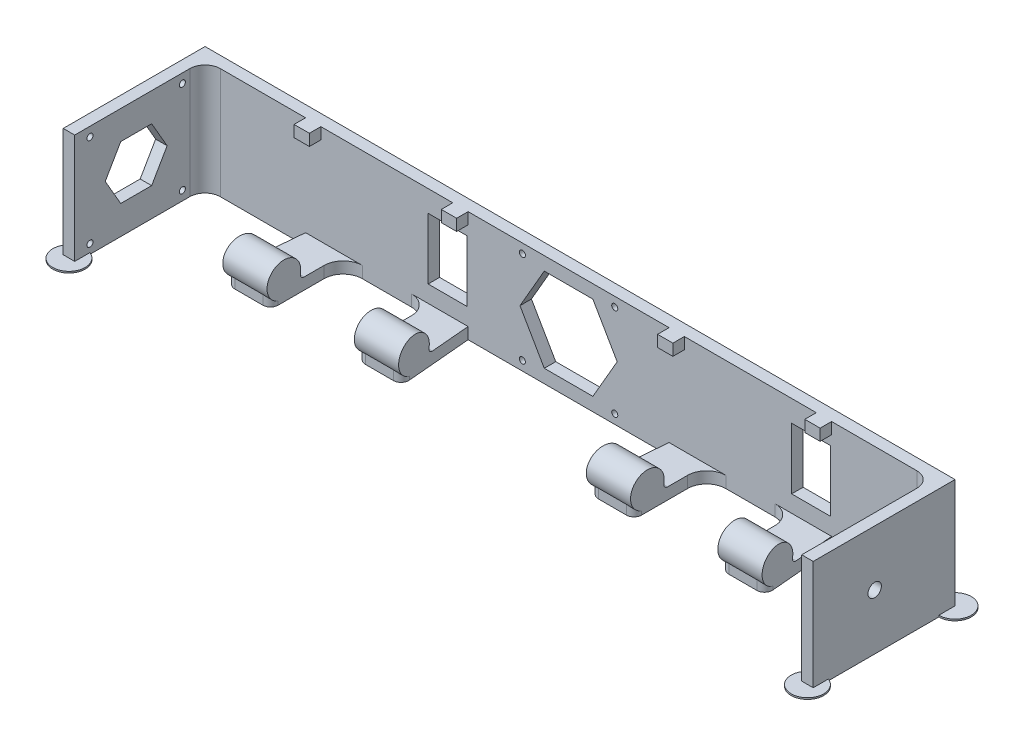
SolidWorks part; units mm, degrees
note: The reader was unsure of these and kept them because the rebuilt part matched: shared geometry of "Sketch10<3>".
ref_plane "Front Plane" through (0, 0, 0) normal (0, 0, 1) x (1, 0, 0)
ref_plane "Top Plane" through (0, 0, 0) normal (0, 1, 0) x (1, 0, 0)
ref_plane "Right Plane" through (0, 0, 0) normal (1, 0, 0) x (0, 0, -1)
sketch "Sketch1" plane through (0, 0, 0) normal (0, 0, 1) x (1, 0, 0)
  line L1 (-95, 14.5) -> (95, 14.5)
  line L2 (-95, 14.5) -> (-95, -14.5)
  line L3 (-95, -14.5) -> (95, -14.5)
  line L4 (95, 14.5) -> (95, -14.5)
  line L5 (-95, 14.5) -> (95, -14.5) construction
  line L6 (-95, -14.5) -> (95, 14.5) construction
  point P0 (0, 0)
  dimension "D1" = 190
  dimension "D2" = 29
extrude "Boss-Extrude1" add sketch "Sketch1" along normal blind 3
sketch "Sketch2" plane through (0, 0, 3) normal (0, 0, 1) x (1, 0, 0)
  line L0 (95, -14.5) -> (95, 14.5) construction
  line L1 (-95, 14.5) -> (95, 14.5)
  line L2 (-95, 14.5) -> (-95, 11.5)
  line L3 (-95, 11.5) -> (95, 11.5)
  line L4 (95, 14.5) -> (95, 11.5)
  dimension "D1" = 3
extrude "Boss-Extrude2" add sketch "Sketch2" along normal blind 3
sketch "Sketch3" plane through (0, 0, 3) normal (0, 0, 1) x (1, 0, 0)
  line L0 (95, -14.5) -> (95, 11.5) construction
  line L1 (-95, -14.5) -> (95, -14.5)
  line L2 (-95, -14.5) -> (-95, -11.5)
  line L3 (-95, -11.5) -> (95, -11.5)
  line L4 (95, -14.5) -> (95, -11.5)
  dimension "D1" = 3
extrude "Boss-Extrude3" add sketch "Sketch3" along normal blind 19
sketch "Sketch4" plane through (-95, 0, 0) normal (-1, 0, 0) x (0, 0, 1)
  line L0 (3, 11.5) -> (3, -11.5) construction
  line L2 (22, -11.5) -> (3, -11.5) construction
  line L3 (6, 14.5) -> (0, 14.5) construction
  circle A0 centre (18.5, -9.4) radius 4.4
  arc A1 (3, 11.5) -> (8.2117, 14.5) centre (18.5, -9.4) cw construction
  point P4 (18.5, -5)
  dimension "D1" = 8.8
  dimension "D3" = 6.5
  dimension "D2" = 15.5
extrude "Boss-Extrude4" add sketch "Sketch4" against normal up to vertex (190 mm away) up to point (95, -11.5, 22)
fillet "Fillet1" radius 1 1 edges at (0, -11.5, 14.6335)
sketch "Sketch5" plane through (0, 0, 3) normal (0, 0, 1) x (1, 0, 0)
  line L1 (-95, -14.5) -> (-70.4, -14.5)
  line L2 (-95, -14.5) -> (-95, -5)
  line L3 (-95, -5) -> (-70.4, -5)
  line L4 (-70.4, -14.5) -> (-70.4, -5)
  line L5 (-58.9, -14.5) -> (-36.1, -14.5)
  line L6 (-58.9, -14.5) -> (-58.9, -5)
  line L7 (-58.9, -5) -> (-36.1, -5)
  line L8 (-36.1, -14.5) -> (-36.1, -5)
  line L9 (0, -5) -> (0, 0) construction
  line L10 (-24.6, -14.5) -> (24.6, -14.5)
  line L11 (-24.6, -14.5) -> (-24.6, -5)
  line L12 (-24.6, -5) -> (24.6, -5)
  line L13 (24.6, -14.5) -> (24.6, -5)
  line L14 (36.1, -14.5) -> (36.1, -5)
  line L15 (58.9, -5) -> (36.1, -5)
  line L16 (58.9, -14.5) -> (58.9, -5)
  line L17 (58.9, -14.5) -> (36.1, -14.5)
  line L18 (70.4, -14.5) -> (70.4, -5)
  line L19 (95, -5) -> (70.4, -5)
  line L20 (95, -14.5) -> (95, -5)
  line L21 (95, -14.5) -> (70.4, -14.5)
  line L22 (95, -5) -> (-95, -5) construction
  line L23 (-95, -14.5) -> (95, -14.5) construction
  dimension "D1" = 11.5
  dimension "D2" = 11.5
  dimension "D3" = 95
  dimension "D4" = 22.8
  dimension "D5" = 45.8
extrude "Cut-Extrude1" cut sketch "Sketch5" along normal through all
sketch "Sketch8" plane through (0, 0, 3) normal (0, 0, 1) x (1, 0, 0)
  line L1 (6.3509, -11) -> (12.7017, 0)
  line L2 (12.7017, 0) -> (6.3509, 11)
  line L3 (6.3509, 11) -> (-6.3509, 11)
  line L4 (-6.3509, 11) -> (-12.7017, 0)
  line L5 (-12.7017, 0) -> (-6.3509, -11)
  line L6 (-6.3509, -11) -> (6.3509, -11)
  circle A0 centre (-12.0668, -12.0668) radius 0.7937
  circle A1 centre (-12.0668, 12.0668) radius 0.7937
  circle A2 centre (12.0668, 12.0668) radius 0.7937
  circle A3 centre (12.0668, -12.0668) radius 0.7937
  circle A4 centre (0, 0) radius 11 construction
  point P10 (0, 0)
  dimension "D2" = 34.13
  dimension "D3" = 1.5875
  dimension "D4" = 22
  dimension "D1" = 4
extrude "Cut-Extrude3" cut sketch "Sketch8" against normal up to next
sketch "Sketch9" plane through (0, 0, 3) normal (0, 0, 1) x (1, 0, 0)
  line L0 (-58.9, -14.5) -> (-36.1, -14.5) construction
  line L1 (-36.7, 8.9) -> (-26.5, 8.9)
  line L2 (-36.7, 8.9) -> (-36.7, -7.1)
  line L3 (-36.7, -7.1) -> (-26.5, -7.1)
  line L4 (-26.5, 8.9) -> (-26.5, -7.1)
  line L5 (-36.1, -14.5) -> (-36.1, -11.5) construction
  line L6 (-31.6, -5.1) -> (-31.6, -7.1) construction
  line L7 (-24.6, -11.5) -> (70.4, -11.5) construction
  line L8 (15.9, -11.5) -> (15.9, -1.9782) construction
  line L9 (68.5, 8.9) -> (68.5, -7.1)
  line L10 (68.5, -7.1) -> (58.3, -7.1)
  line L11 (58.3, 8.9) -> (58.3, -7.1)
  line L12 (68.5, 8.9) -> (58.3, 8.9)
  line L13 (-26.5, 8.9) -> (68.5, 8.9) construction
  point P4 (-31.6, -5.1)
  dimension "D1" = 10.2
  dimension "D2" = 16
  dimension "D3" = 9.4
  dimension "D4" = 4.5
  dimension "D5" = 2
extrude "Cut-Extrude4" cut sketch "Sketch9" against normal up to next
draft "Draft1" type of draft neutral plane draft angle 5 faces to draft 4 face at (70.4, -11.4205, 13.1781) face at (24.6, -11.4205, 13.1781) face at (-24.6, -11.4205, 13.1781) face at (-70.4, -11.4205, 13.1781) neutral plane through (0, 0, 22) neutral plane normal (0, 0, 1) reverse direction yes parameters "D1"=5
fillet "Fillet2" radius 5 4 edges at (36.1, -13, 3) (58.9, -13, 3) (-36.1, -13, 3) (-58.9, -13, 3)
fillet "Fillet3" radius 2 8 edges at (70.4, -13.2832, 22) (58.9, -13.2832, 22) (36.1, -13.2832, 22) (24.6, -13.2832, 22) (-24.6, -13.2832, 22) (-36.1, -13.2832, 22) (-58.9, -13.2832, 22) (-70.4, -13.2832, 22)
sketch "Sketch10" plane through (-95, 0, 0) normal (-1, 0, 0) x (0, 0, 1)
  line L0 (3, -14.5) -> (0, -14.5) construction
  line L1 (0, 14.5) -> (8.9297, 14.5)
  line L2 (0, 14.5) -> (0, -14.5)
  line L3 (0, -14.5) -> (37.0703, -14.5)
  line L5 (3, 11.5) -> (3, -14.5) construction
  line L6 (6, 11.5) -> (3, 11.5) construction
  line L7 (8.9297, 14.5) -> (37.0703, 14.5)
  line L8 (37.0703, 14.5) -> (37.0703, -14.5)
  line L9 (29.0829, 0) -> (25.0415, 7)
  line L10 (25.0415, 7) -> (16.9585, 7)
  line L11 (16.9585, 7) -> (12.9171, 0)
  line L12 (12.9171, 0) -> (16.9585, -7)
  line L13 (16.9585, -7) -> (25.0415, -7)
  line L14 (25.0415, -7) -> (29.0829, 0)
  circle A1 centre (8.9297, 12.0703) radius 0.7938
  circle A2 centre (33.0703, 12.0703) radius 0.7937
  circle A3 centre (33.0703, -12.0703) radius 0.7937
  circle A4 centre (8.9297, -12.0703) radius 0.7937
  circle A5 centre (21, 0) radius 1.75
  circle A6 centre (21, 0) radius 7 construction
  point P30 (21, 0)
  dimension "D4" = 4
  dimension "D6" = 34.14
  dimension "D7" = 1.5875
  dimension "D8" = 3.5
  dimension "D1" = 14
  dimension "D2" = 11.5
  dimension "D3" = 18
  dimension "D5" = 4
extrude "Boss-Extrude5" add sketch "Sketch10" along normal blind 3
extrude "Boss-Extrude8" add sketch "Sketch10<3>" against normal blind 3 from vertex at -190 contours L7 L8 L3 L2 L1 | A5
sketch "Sketch10<3>" plane through (-95, 0, 0) normal (-1, 0, 0) x (0, 0, 1) same geometry as "Sketch10"
sketch "Sketch12" plane through (0, 0, 3) normal (0, 0, 1) x (1, 0, 0)
  line L0 (95, 14.5) -> (-95, 14.5) construction
  line L1 (-95, 11.5) -> (-68.7377, 11.5)
  line L2 (-95, 11.5) -> (-95, 14.5)
  line L3 (-95, 14.5) -> (-68.7377, 14.5)
  line L4 (-68.7377, 11.5) -> (-68.7377, 14.5)
  line L5 (-95, 11.5) -> (-12.6225, 11.5) construction
  line L7 (-95, 11.5) -> (-12.6225, 11.5) construction
  line L8 (-64.7377, 14.5) -> (-30.2623, 14.5)
  line L9 (-64.7377, 14.5) -> (-64.7377, 11.5)
  line L10 (-64.7377, 11.5) -> (-30.2623, 11.5)
  line L11 (-30.2623, 14.5) -> (-30.2623, 11.5)
  line L12 (12.6225, 11.5) -> (95, 11.5) construction
  line L13 (-26.2623, 14.5) -> (26.2623, 14.5)
  line L14 (-26.2623, 14.5) -> (-26.2623, 11.5)
  line L15 (-26.2623, 11.5) -> (26.2623, 11.5)
  line L16 (26.2623, 14.5) -> (26.2623, 11.5)
  line L17 (30.2623, 14.5) -> (64.7377, 14.5)
  line L18 (30.2623, 14.5) -> (30.2623, 11.5)
  line L19 (30.2623, 11.5) -> (64.7377, 11.5)
  line L20 (64.7377, 14.5) -> (64.7377, 11.5)
  line L21 (68.7377, 14.5) -> (95, 14.5)
  line L22 (68.7377, 14.5) -> (68.7377, 11.5)
  line L23 (68.7377, 11.5) -> (95, 11.5)
  line L24 (95, 14.5) -> (95, 11.5)
  line L26 (68.7377, -11.5) -> (68.7377, -14.5) construction
  line L27 (-68.7377, -14.5) -> (-68.7377, -11.5) construction
  line L28 (-26.2623, -11.5) -> (-26.2623, -14.5) construction
  line L29 (26.2623, -14.5) -> (26.2623, -11.5) construction
  line L30 (95, 11.5) -> (95, 14.5) construction
  line L31 (-95, 14.5) -> (-95, 11.5) construction
  dimension "D4" = 4
  dimension "D5" = 4
  dimension "D6" = 4
  dimension "D7" = 4
extrude "Cut-Extrude5" cut sketch "Sketch12" along normal through all
sketch "Sketch13" plane through (0, -14.5, 0) normal (0, -1, 0) x (1, 0, 0)
  line L0 (-98, 37.0703) -> (-95, 37.0703) construction
  line L1 (98, 37.0703) -> (95, 37.0703) construction
  circle A0 centre (-96.5, 37.0703) radius 4.2426
  circle A1 centre (96.5, 37.0703) radius 4.2426
  circle A2 centre (98, 0) radius 4.2426
  circle A3 centre (-98, 0) radius 4.2426
extrude "Boss-Extrude9" add sketch "Sketch13" against normal blind 0.4
fillet "Fillet4" radius 4 2 edges
